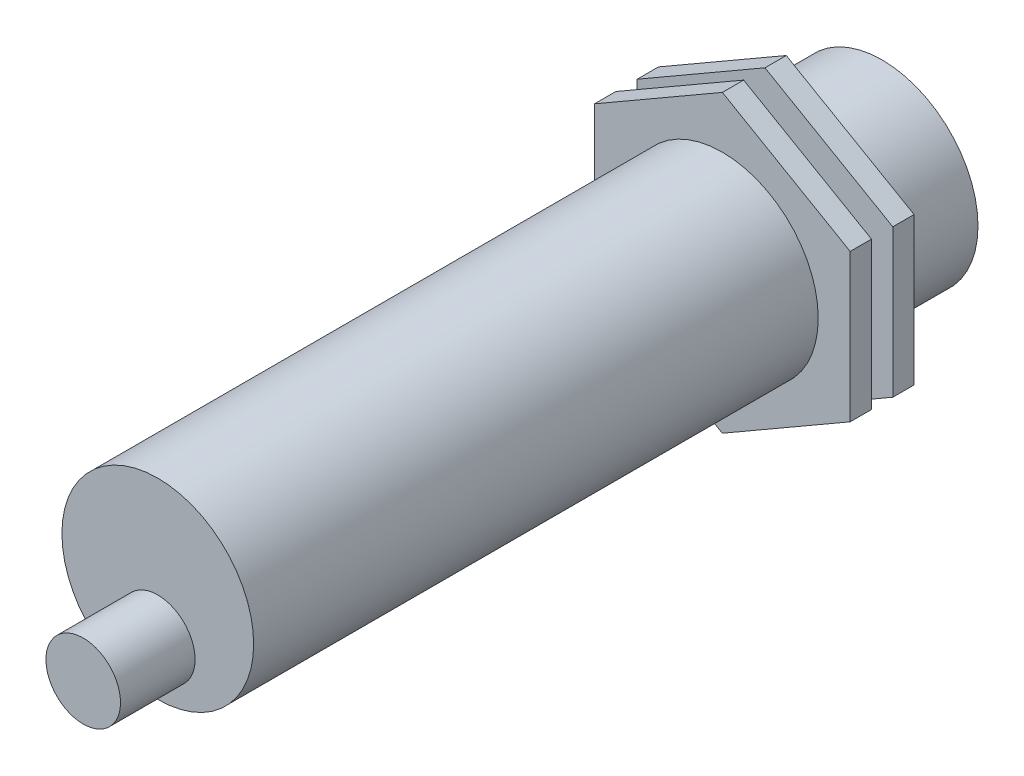
SolidWorks part; units mm, degrees
ref_plane "Front Plane" through (0, 0, 0) normal (0, 0, 1) x (1, 0, 0)
ref_plane "Top Plane" through (0, 0, 0) normal (0, 1, 0) x (1, 0, 0)
ref_plane "Right Plane" through (0, 0, 0) normal (1, 0, 0) x (0, 0, -1)
sketch "Sketch1" plane through (0, 0, 0) normal (0, 0, 1) x (1, 0, 0)
  circle A0 centre (0, 0) radius 9
  dimension "D1" = 18
extrude "Boss-Extrude1" add sketch "Sketch1" along normal blind 68
sketch "Sketch2" plane through (0, 0, 68) normal (0, 0, 1) x (1, 0, 0)
  line L0 (0, -9.9) -> (0, 9.9) construction
  circle A0 centre (0, -4) radius 3.5
  circle A1 centre (0, 0) radius 9 construction
  dimension "D1" = 7
  dimension "D2" = 4
extrude "Boss-Extrude2" add sketch "Sketch2" along normal blind 7
ref_plane "Plane1" through (0, 0, 9) normal (0, 0, -1) x (-1, 0, 0)
sketch "Sketch4" plane through (0, 0, 9) normal (0, 0, -1) x (-1, 0, 0)
  line L0 (-12, 6.9282) -> (-12, -6.9282)
  line L1 (-12, -6.9282) -> (0, -13.8564)
  line L2 (0, -13.8564) -> (12, -6.9282)
  line L3 (12, -6.9282) -> (12, 6.9282)
  line L4 (12, 6.9282) -> (0, 13.8564)
  line L5 (0, 13.8564) -> (-12, 6.9282)
  line L6 (-12, 6.9282) -> (12, -6.9282) construction
  line L7 (12, 6.9282) -> (-12, -6.9282) construction
  line L8 (0, 9.9) -> (0, -9.9) construction
  line L9 (0, 13.8564) -> (0, -13.8564) construction
  point P0 (0, 15.5432)
  dimension "D1" = 24
  dimension "D2" = 120
extrude "Boss-Extrude3" add sketch "Sketch4" against normal blind 2
extrude "Boss-Extrude4" add sketch "Sketch4<2>" along normal blind 2 from offset 6 offset against normal yes
sketch "Sketch4<2>" plane through (0, 0, 9) normal (0, 0, -1) x (-1, 0, 0) same geometry as "Sketch4"
